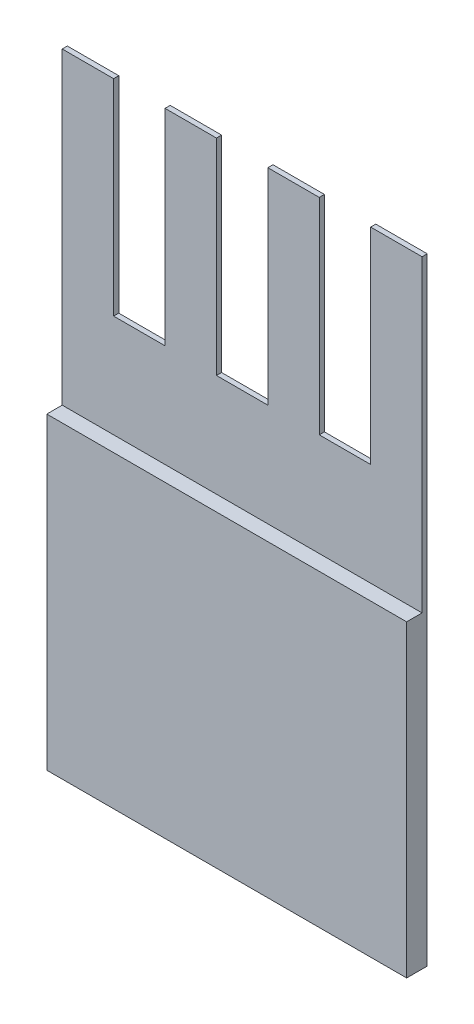
SolidWorks part; units mm, degrees
ref_plane "Front" through (0, 0, 0) normal (0, 0, 1) x (1, 0, 0)
ref_plane "Top" through (0, 0, 0) normal (0, 1, 0) x (1, 0, 0)
ref_plane "Side" through (0, 0, 0) normal (1, 0, 0) x (0, 0, -1)
sketch "Sketch1" plane through (0, 0, 0) normal (0, 0, 1) x (1, 0, 0)
  line L0 (-12.5, 30) -> (-17.5, 30)
  line L1 (17.5, 30) -> (12.5, 30)
  line L2 (17.5, 30) -> (17.5, -30)
  line L3 (17.5, -30) -> (-17.5, -30)
  line L4 (-17.5, 30) -> (-17.5, -30)
  line L5 (-2.5, 10) -> (2.5, 10)
  line L6 (-12.5, 10) -> (-7.5, 10)
  line L7 (-17.5, 30) -> (-12.5, 30)
  line L8 (-17.5, 30) -> (-17.5, 10)
  line L9 (-12.5, 10) -> (-7.5, 10)
  line L10 (17.5, 30) -> (17.5, 10)
  line L20 (-2.5, 30) -> (-2.5, 10)
  line L21 (-2.5, 10) -> (2.5, 10)
  line L22 (2.5, 30) -> (2.5, 10)
  line L24 (-7.5, 30) -> (-7.5, 10)
  line L25 (-7.5, 10) -> (-12.5, 10)
  line L26 (-12.5, 30) -> (-12.5, 10)
  line L28 (7.5, 30) -> (7.5, 10)
  line L29 (7.5, 10) -> (12.5, 10)
  line L30 (12.5, 30) -> (12.5, 10)
  line L31 (-7.5, 30) -> (-2.5, 30)
  line L32 (-17.5, 10) -> (-17.5, 0)
  line L33 (-2.5, 30) -> (-7.5, 30)
  line L34 (2.5, 30) -> (7.5, 30)
  line L35 (7.5, 30) -> (2.5, 30)
  line L36 (12.5, 30) -> (17.5, 30)
  line L37 (-17.5, 0) -> (17.5, 0)
  line L38 (17.5, 10) -> (17.5, 0)
  line L39 (-2.5, 10) -> (2.5, 10)
  line L40 (7.5, 10) -> (12.5, 10)
  line L41 (7.5, 10) -> (12.5, 10)
  point P0 (0, 0)
extrude "Boss-Extrude5" add sketch "Sketch1" along normal blind 2 contours L37 L4 L3 L2 region at (0, -15, 0)
extrude "Boss-Extrude6" add sketch "Sketch1<7>" along normal blind 0.5 contours L4 L37 L2 L1 L30 L29 L28 L34 L22 L5 L20 L31 L24 L6 L26 L0 region at (-12.961, 20, 0)
sketch "Sketch1<7>" plane through (0, 0, 0) normal (0, 0, 1) x (1, 0, 0) same geometry as "Sketch1"
